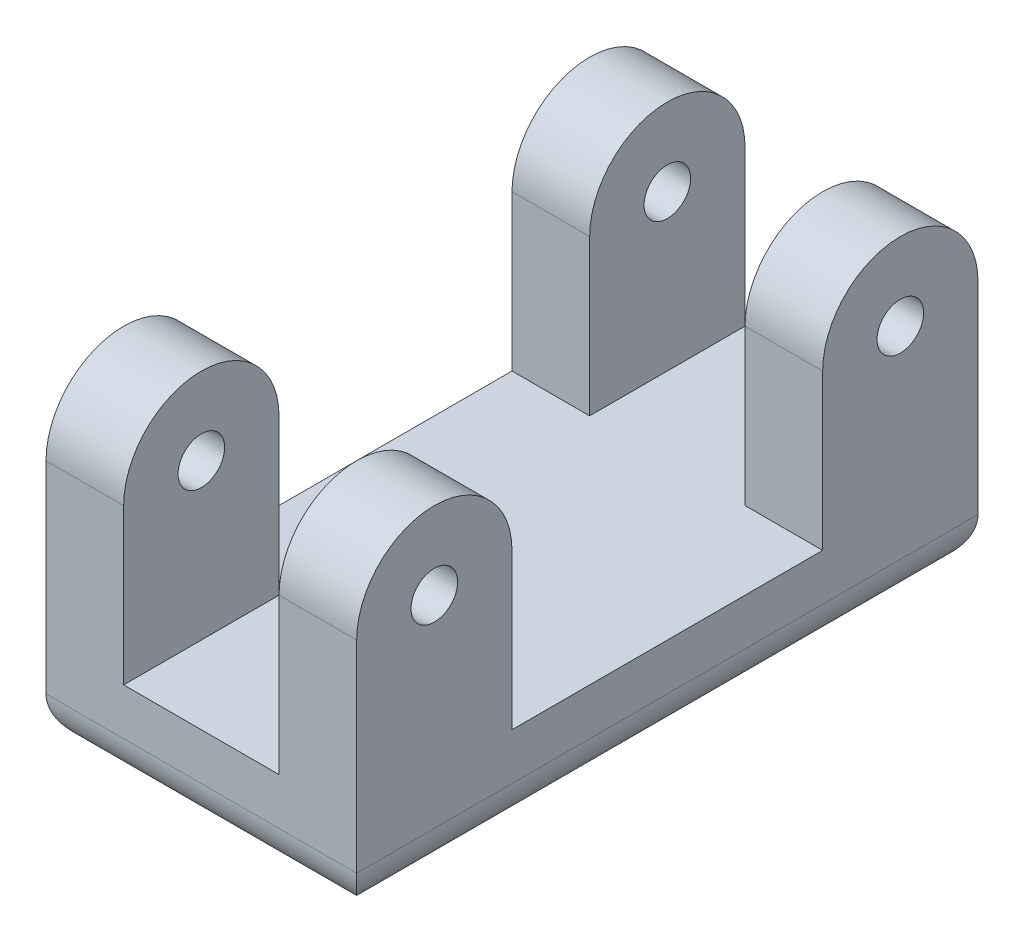
SolidWorks part; units mm, degrees
ref_plane "Front Plane" through (0, 0, 0) normal (0, 0, 1) x (1, 0, 0)
ref_plane "Top Plane" through (0, 0, 0) normal (0, 1, 0) x (1, 0, 0)
ref_plane "Right Plane" through (0, 0, 0) normal (1, 0, 0) x (0, 0, -1)
sketch "Sketch1" plane through (0, 0, 0) normal (0, 0, 1) x (1, 0, 0)
  line L1 (-10, 3) -> (10, 3)
  line L2 (-10, 3) -> (-10, -3)
  line L3 (-10, -3) -> (10, -3)
  line L4 (10, 3) -> (10, -3)
  line L5 (-10, 3) -> (10, -3) construction
  line L6 (-10, -3) -> (10, 3) construction
  point P0 (0, 0)
  dimension "D1" = 6
  dimension "D2" = 20
extrude "Boss-Extrude1" add sketch "Sketch1" along normal blind 20 and the other way blind 20
sketch "Sketch2" plane through (10, 0, 0) normal (1, 0, 0) x (0, 0, -1)
  line L1 (-20, 3) -> (-10, 3)
  line L2 (-20, 3) -> (-20, 13)
  line L3 (-20, 13) -> (-10, 13)
  line L4 (-10, 3) -> (-10, 13)
  line L5 (20, 3) -> (10, 3)
  line L6 (20, 3) -> (20, 13)
  line L7 (20, 13) -> (10, 13)
  line L8 (10, 3) -> (10, 13)
  circle A0 centre (-15, 13) radius 5
  circle A1 centre (-15, 13) radius 1.5
  circle A2 centre (15, 13) radius 5
  circle A3 centre (15, 13) radius 1.5
  line M7 (20, 3) -> (-20, 3)
  dimension "D5" = 3
  dimension "D6" = 3
  dimension "D1" = 10
  dimension "D2" = 10
  dimension "D3" = 10
  dimension "D4" = 10
extrude "Boss-Extrude2" add sketch "Sketch2" against normal blind 20 contours A0 L2 L4 M7 | A1 L3 A0 | A1 L3 A0 | A3 L7 A2 | A3 L7 A2 | A2 L8 L6 M7 region at (10, 6.139, 15) region at (10, 6.139, -15) region at (10, 15.269, 15) region at (10, 10.731, 15) region at (10, 15.269, -15) region at (10, 10.731, -15)
sketch "Sketch3" plane through (0, 0, 20) normal (0, 0, 1) x (1, 0, 0)
  line L0 (10, 18) -> (-10, 18) construction
  line L1 (-5, 18) -> (5, 18)
  line L2 (-5, 18) -> (-5, 3)
  line L3 (-5, 3) -> (5, 3)
  line L4 (5, 18) -> (5, 3)
  line L5 (10, 13) -> (10, 18) construction
  dimension "D1" = 10
  dimension "D2" = 5
  dimension "D3" = 15
extrude "Cut-Extrude1" cut sketch "Sketch3" against normal blind 40
fillet "Fillet2" radius 3 4 edges at (0, -3, -20) (-10, -3, 0) (0, -3, 20) (10, -3, 0)
